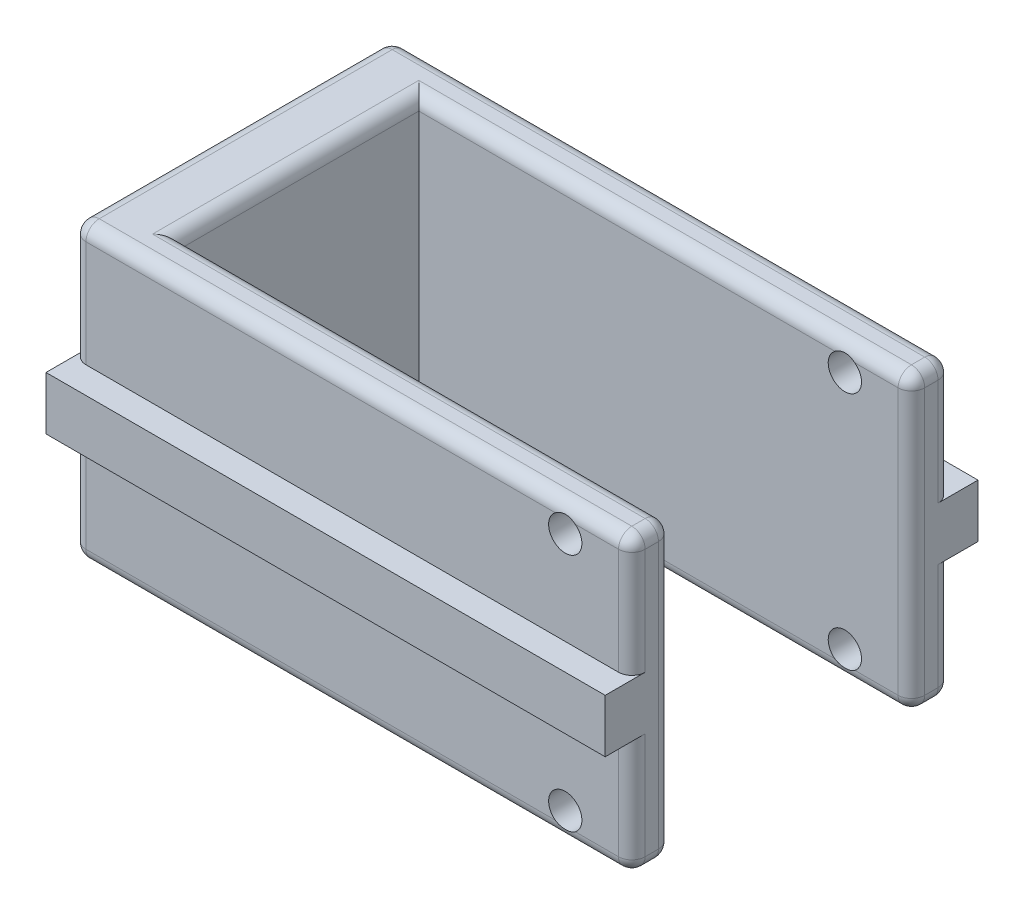
SolidWorks part; units mm, degrees
material "Cast Alloy Steel"
ref_plane "Front Plane" through (0, 0, 0) normal (0, 0, 1) x (1, 0, 0)
ref_plane "Top Plane" through (0, 0, 0) normal (0, 1, 0) x (1, 0, 0)
ref_plane "Right Plane" through (0, 0, 0) normal (1, 0, 0) x (0, 0, -1)
sketch "Sketch1" plane through (0, 0, 0) normal (0, 1, 0) x (1, 0, 0)
  line L0 (0, 0) -> (-42, 0)
  line L1 (-42, 0) -> (-42, 24)
  line L2 (-42, 24) -> (0, 24)
  line L3 (0, 24) -> (0, 21)
  line L4 (0, 21) -> (-37, 21)
  line L5 (-37, 21) -> (-37, 3)
  line L6 (-37, 3) -> (0, 3)
  line L7 (0, 3) -> (0, 0)
  dimension "D1" = 18
  dimension "D2" = 3
  dimension "D3" = 37
  dimension "D4" = 42
extrude "Boss-Extrude1" add sketch "Sketch1" along normal blind 22
sketch "Sketch2" plane through (0, 0, 0) normal (0, 0, 1) x (1, 0, 0)
  line L0 (-5, 22) -> (-5, 20) construction
  line L1 (-42, 22) -> (0, 22) construction
  line L2 (-5, 20) -> (0, 20) construction
  line L3 (0, 22) -> (0, 0) construction
  line L5 (-5, 2) -> (-5, 0) construction
  line L6 (-42, 0) -> (0, 0) construction
  line L8 (0, 2) -> (-5, 2) construction
  circle A0 centre (-5, 20) radius 1.25
  circle A1 centre (-5, 2) radius 1.25
  dimension "D3" = 2.5
  dimension "D1" = 2
  dimension "D2" = 5
extrude "Cut-Extrude1" cut sketch "Sketch2" against normal through all
sketch "Sketch3" plane through (-42, 0, 0) normal (-1, 0, 0) x (0, 0, 1)
  line L0 (-12, 22) -> (-12, 0) construction
  line L1 (-24, 22) -> (0, 22) construction
  line L2 (-24, 0) -> (0, 0) construction
  circle A0 centre (-12, 11) radius 2.5
  dimension "D1" = 5
extrude "Boss-Extrude2" add sketch "Sketch3" along normal blind 5
fillet "Fillet1" radius 1 1 edges at (-42, 11, -9.5)
sketch "Sketch4" plane through (-42, 0, 0) normal (-1, 0, 0) x (0, 0, 1)
  line L0 (-24, 22) -> (-24, 0) construction
  line L1 (-22, 9) -> (-26, 9)
  line L2 (-22, 9) -> (-22, 13)
  line L3 (-22, 13) -> (-26, 13)
  line L4 (-26, 9) -> (-26, 13)
  line L5 (-22, 9) -> (-26, 13) construction
  line L6 (-22, 13) -> (-26, 9) construction
  line L7 (0, 22) -> (0, 0) construction
  line L8 (-2, 9) -> (2, 9)
  line L9 (-2, 9) -> (-2, 13)
  line L10 (-2, 13) -> (2, 13)
  line L11 (2, 9) -> (2, 13)
  line L12 (-2, 9) -> (2, 13) construction
  line L13 (-2, 13) -> (2, 9) construction
  point P0 (-24, 11)
  point P7 (0, 11)
  dimension "D1" = 4
  dimension "D2" = 4
extrude "Boss-Extrude3" add sketch "Sketch4" against normal blind 42
fillet "Fillet2" radius 1 2 edges at (-42, 0, -12) (-42, 22, -12)
fillet "Fillet3" radius 1 11 edges at (-42, 17, 0) (-41.7071, 21.7071, 0) (-42, 17, -24) (-41.7071, 21.7071, -24) (0, 22, -22.5) (-18.5, 22, -21) (-37, 22, -12) (-18.5, 22, -3) (0, 22, -1.5) (-20.5, 22, 0) (-20.5, 22, -24)
fillet "Fillet4" radius 1 11 edges at (-42, 5, -24) (-41.7071, 0.2929, -24) (-42, 5, 0) (-41.7071, 0.2929, 0) (0, 0, -1.5) (-18.5, 0, -3) (-37, 0, -12) (-18.5, 0, -21) (0, 0, -22.5) (-20.5, 0, -24) (-20.5, 0, 0)
fillet "Fillet5" radius 1 14 edges at (-0.2929, 0.2929, -23.7071) (-0.2929, 21.7071, -23.7071) (-0.2929, 21.7071, -21.2929) (-0.2929, 0.2929, -21.2929) (-0.2929, 21.7071, -2.7071) (-0.2929, 0.2929, -2.7071) (-0.2929, 0.2929, -0.2929) (-0.2929, 21.7071, -0.2929) (0, 5, -24) (0, 17, -24) (0, 11, -21) (0, 11, -3) (0, 5, 0) (0, 17, 0)
